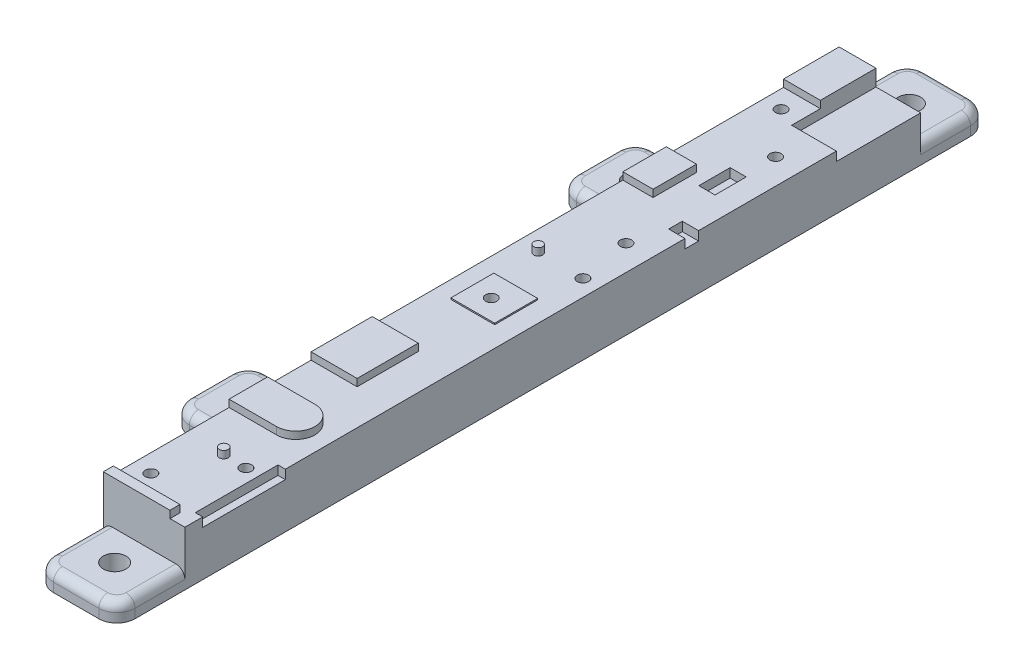
SolidWorks part; units mm, degrees
ref_plane "Front Plane" through (0, 0, 0) normal (0, 0, 1) x (1, 0, 0)
ref_plane "Top Plane" through (0, 0, 0) normal (0, 1, 0) x (1, 0, 0)
ref_plane "Right Plane" through (0, 0, 0) normal (1, 0, 0) x (0, 0, -1)
sketch "Sketch1" plane through (0, 0, 0) normal (0, 1, 0) x (1, 0, 0)
  line L1 (0, 0) -> (-18, 0)
  line L2 (0, 0) -> (0, -162.4)
  line L3 (0, -162.4) -> (-18, -162.4)
  line L4 (-18, 0) -> (-18, -162.4)
  line L5 (-18, 0) -> (-9.87, 0)
  line L6 (-18, 0) -> (-18, -12.28)
  line L7 (-18, -12.28) -> (-9.87, -12.28)
  line L8 (-9.87, 0) -> (-9.87, -12.28)
  line L9 (-18, -38.15) -> (-11.34, -38.15)
  line L10 (-18, -38.15) -> (-18, -47.73)
  line L11 (-18, -47.73) -> (-11.34, -47.73)
  line L12 (-11.34, -38.15) -> (-11.34, -47.73)
  line L13 (-18, -103.06) -> (-7.83, -103.06)
  line L14 (-18, -103.06) -> (-18, -116.55)
  line L15 (-18, -116.55) -> (-7.83, -116.55)
  line L16 (-7.83, -103.06) -> (-7.83, -116.55)
  line L17 (-18, -160.19) -> (-3.29, -160.19)
  line L18 (-18, -160.19) -> (-18, -162.4)
  line L19 (-18, -162.4) -> (-3.29, -162.4)
  line L20 (-3.29, -160.19) -> (-3.29, -162.4)
  line L21 (-14.18, -80.03) -> (-4.51, -80.03)
  line L22 (-14.18, -80.03) -> (-14.18, -89.52)
  line L23 (-14.18, -89.52) -> (-4.51, -89.52)
  line L24 (-4.51, -80.03) -> (-4.51, -89.52)
  line L25 (-18, -126.15) -> (-7.53, -126.15)
  line L26 (-18, -126.15) -> (-18, -134.64)
  line L27 (-18, -134.64) -> (-7.53, -134.64)
  line L28 (-7.53, -126.15) -> (-7.53, -134.64)
  arc A0 (-7.53, -134.64) -> (-7.53, -126.15) centre (-7.53, -130.395) ccw
  dimension "D1" = 162.4
  dimension "D2" = 18
  dimension "D3" = 14.71
  dimension "D4" = 2.21
  dimension "D5" = 8.49
  dimension "D6" = 27.76
  dimension "D7" = 10.47
  dimension "D8" = 13.49
  dimension "D9" = 45.85
  dimension "D10" = 10.17
  dimension "D11" = 8.13
  dimension "D12" = 12.28
  dimension "D13" = 9.58
  dimension "D14" = 6.66
  dimension "D15" = 38.15
  dimension "D16" = 9.49
  dimension "D17" = 9.67
  dimension "D18" = 3.82
  dimension "D19" = 72.88
extrude "Boss-Extrude1" add sketch "Sketch1" against normal blind 12 contours A0 L27 L4 L17 L20 L3 L2 L1 L8 L7 L9 L12 L11 L13 L16 L15 L25 L21 L24 L23 L22 | L24 L21 L22 L23 | L12 L9 L4 L11 | L8 L1 L4 L7 | L16 L13 L4 L15 | L28 L25 L4 L27 | L28 A0 | L20 L17 L4 L3 region at (-1.6339, 0, 81.2) region at (-13.935, 0, 6.14) region at (-10.645, 0, 161.295) region at (-14.67, 0, 42.94) region at (-12.765, 0, 130.395) region at (-12.915, 0, 109.805) region at (-5.7284, 0, 130.395) region at (-9.345, 0, 84.775)
extrude "Boss-Extrude2" add sketch "Sketch1<4>" along normal blind 1.6 contours L20 L17 L4 L3 | L28 L25 L4 L27 | L28 A0 | L16 L13 L4 L15 | L12 L9 L4 L11 | L8 L1 L4 L7 region at (-13.935, 0, 6.14) region at (-10.645, 0, 161.295) region at (-14.67, 0, 42.94) region at (-12.765, 0, 130.395) region at (-12.915, 0, 109.805) region at (-5.7284, 0, 130.395)
sketch "Sketch1<4>" plane through (0, 0, 0) normal (0, 1, 0) x (1, 0, 0) same geometry as "Sketch1"
extrude "Boss-Extrude3" add sketch "Sketch1<5>" along normal blind 0.3 contours L24 L21 L22 L23 region at (-9.345, 0, 84.775)
sketch "Sketch1<5>" plane through (0, 0, 0) normal (0, 1, 0) x (1, 0, 0) same geometry as "Sketch1"
sketch "Sketch2" plane through (0, 0, 162.4) normal (0, 0, 1) x (1, 0, 0)
  line L0 (-18, -12) -> (-18, 1.6) construction
  line L1 (-18, -8) -> (0, -8)
  line L2 (-18, -8) -> (-18, -12)
  line L3 (-18, -12) -> (0, -12)
  line L4 (0, -8) -> (0, -12)
  dimension "D1" = 4
extrude "Boss-Extrude4" add sketch "Sketch2" along normal blind 15
sketch "Sketch3" plane through (0, 0, 0) normal (0, 0, -1) x (-1, 0, 0)
  line L0 (0, -12) -> (0, 0) construction
  line L1 (0, -8) -> (18, -8)
  line L2 (0, -8) -> (0, -12)
  line L3 (0, -12) -> (18, -12)
  line L4 (18, -8) -> (18, -12)
  dimension "D1" = 4
extrude "Boss-Extrude5" add sketch "Sketch3" along normal blind 15
sketch "Sketch4" plane through (-18, 0, 0) normal (-1, 0, 0) x (0, 0, 1)
  line L0 (-15, -12) -> (177.4, -12) construction
  line L1 (30, -12) -> (47, -12)
  line L2 (30, -12) -> (30, -8)
  line L3 (30, -8) -> (47, -8)
  line L4 (47, -12) -> (47, -8)
  line L5 (-15, -12) -> (-15, -8) construction
  line L6 (115.4, -12) -> (132.4, -12)
  line L7 (115.4, -12) -> (115.4, -8)
  line L8 (115.4, -8) -> (132.4, -8)
  line L9 (132.4, -12) -> (132.4, -8)
  line L10 (177.4, -8) -> (177.4, -12) construction
  dimension "D1" = 17
  dimension "D2" = 45
  dimension "D3" = 45
  dimension "D4" = 4
extrude "Boss-Extrude6" add sketch "Sketch4" along normal blind 15
fillet "Fillet1" radius 4 8 edges at (0, -10, 177.4) (-18, -10, 177.4) (-33, -10, 132.4) (-33, -10, 115.4) (-33, -10, 47) (-33, -10, 30) (0, -10, -15) (-18, -10, -15)
fillet "Fillet2" radius 2 20 edges at (-23.5, -8, 115.4) (-31.8284, -8, 116.5716) (-33, -8, 123.9) (-31.8284, -8, 131.2284) (0, -8, 167.9) (-1.1716, -8, 176.2284) (-9, -8, 177.4) (-16.8284, -8, 176.2284) (-23.5, -8, 47) (-31.8284, -8, 45.8284) (-33, -8, 38.5) (-31.8284, -8, 31.1716) (0, -8, -5.5) (-1.1716, -8, -13.8284) (-9, -8, -15) (-16.8284, -8, -13.8284) (-23.5, -8, 132.4) (-18, -8, 167.9) (-23.5, -8, 30) (-18, -8, -5.5)
sketch "Sketch5" plane through (0, -8, 0) normal (0, 1, 0) x (1, 0, 0)
  line L0 (-18, -45) -> (-18, -32) construction
  line L1 (-18, -32) -> (-29, -32) construction
  line L2 (-18, -117.4) -> (-29, -117.4) construction
  line L3 (-2, -162.4) -> (-16, -162.4) construction
  line L4 (-16, 0) -> (-2, 0) construction
  line L5 (-2, 0) -> (-2, 11) construction
  circle A0 centre (-9, 6.5) radius 2.5
  circle A1 centre (-24.5, -38.5) radius 2.5
  circle A2 centre (-24.5, -123.9) radius 2.5
  circle A3 centre (-9, -168.9) radius 2.5
  point P8 (0, 0)
  point P9 (0, 0)
  dimension "D1" = 5
  dimension "D2" = 6.5
  dimension "D3" = 6.5
  dimension "D4" = 6.5
  dimension "D5" = 6.5
  dimension "D6" = 6.5
  dimension "D7" = 7
extrude "Cut-Extrude1" cut sketch "Sketch5" against normal up to next
sketch "Sketch6" plane through (0, 0, 0) normal (0, 1, 0) x (1, 0, 0)
  line L0 (-18, -134.64) -> (-18, -160.19) construction
  line L1 (-18, -160.19) -> (-3.29, -160.19) construction
  circle A0 centre (-14.04, -155.86) radius 1.25
  circle A1 centre (-9.46, -144.3448) radius 0.985
  circle A2 centre (-4.59, -144.3448) radius 1.25
  point P10 (0, 0)
  dimension "D1" = 2.5
  dimension "D4" = 2.5
  dimension "D5" = 1.97
  dimension "D2" = 3.96
  dimension "D3" = 4.33
  dimension "D6" = 8.54
  dimension "D7" = 13.41
extrude "Boss-Extrude7" add sketch "Sketch6" along normal blind 1.6 contours A1 region at (-9.46, 0, 144.3448)
extrude "Cut-Extrude2" cut sketch "Sketch6<3>" against normal up to next contours A0 | A2 region at (-14.04, 0, 155.86) region at (-4.59, 0, 144.3448)
sketch "Sketch6<3>" plane through (0, 0, 0) normal (0, 1, 0) x (1, 0, 0) same geometry as "Sketch6"
sketch "Sketch7" plane through (0, 0.3, 0) normal (0, 1, 0) x (1, 0, 0)
  line L0 (-18, -47.73) -> (-18, -103.06) construction
  line L1 (-18, -160.19) -> (-3.29, -160.19) construction
  circle A0 centre (-9.705, -85.075) radius 1.25
  point P2 (0, 0)
  dimension "D1" = 2.5
  dimension "D2" = 8.295
  dimension "D3" = 75.115
extrude "Cut-Extrude3" cut sketch "Sketch7" against normal up to next
sketch "Sketch8" plane through (0, 0, 0) normal (0, 1, 0) x (1, 0, 0)
  line L0 (-18, -47.73) -> (-18, -103.06) construction
  line L1 (0, -162.4) -> (-3.29, -162.4) construction
  circle A0 centre (-13.505, -70.905) radius 0.97
  circle A1 centre (-3.64, -70.905) radius 1.25
  point P4 (0, 0)
  dimension "D1" = 1.94
  dimension "D2" = 2.5
  dimension "D5" = 91.495
  dimension "D3" = 4.495
  dimension "D4" = 14.36
extrude "Boss-Extrude8" add sketch "Sketch8" along normal blind 1.6 contours A0 region at (-13.505, 0, 70.905)
extrude "Cut-Extrude4" cut sketch "Sketch8<3>" against normal up to next contours A1 region at (-3.64, 0, 70.905)
sketch "Sketch8<3>" plane through (0, 0, 0) normal (0, 1, 0) x (1, 0, 0) same geometry as "Sketch8"
sketch "Sketch9" plane through (0, 0, 0) normal (0, 1, 0) x (1, 0, 0)
  line L0 (-18, -47.73) -> (-18, -103.06) construction
  line L1 (0, 0) -> (-9.87, 0) construction
  line L2 (-18, -12.28) -> (-18, -38.15) construction
  line L3 (-18, -12.28) -> (-9.87, -12.28) construction
  line L4 (-9.87, 0) -> (-9.87, -12.28) construction
  line L5 (0, 0) -> (-9.87, 0)
  line L6 (0, 0) -> (0, -18.61)
  line L7 (0, -18.61) -> (-9.87, -18.61)
  line L8 (-9.87, 0) -> (-9.87, -18.61)
  circle A0 centre (-5.61, -59.44) radius 1.25
  circle A1 centre (-5.61, -26.42) radius 1.25
  circle A2 centre (-14.09, -16.73) radius 1.25
  point P22 (0, 0)
  line M12 (-9.87, 0) -> (-9.87, -12.28)
  line M30 (0, -162.4) -> (0, 0)
  line M31 (0, 0) -> (-9.87, 0)
  dimension "D1" = 2.5
  dimension "D4" = 2.5
  dimension "D6" = 2.5
  dimension "D2" = 12.39
  dimension "D3" = 59.44
  dimension "D5" = 26.42
  dimension "D7" = 3.91
  dimension "D8" = 4.45
  dimension "D9" = 18.61
extrude "Cut-Extrude5" cut sketch "Sketch9" against normal up to next contours A0 | A1 | A2 region at (-5.61, 0, 59.44) region at (-5.61, 0, 26.42) region at (-14.09, 0, 16.73)
extrude "Cut-Extrude6" cut sketch "Sketch9<3>" against normal blind 1.6
sketch "Sketch9<3>" plane through (0, 0, 0) normal (0, 1, 0) x (1, 0, 0) same geometry as "Sketch9"
extrude "Cut-Extrude9" cut sketch "Sketch9<4>" against normal blind 2 contours L8 L7 M12 M30 M31 region at (-4.935, 0, 9.305)
sketch "Sketch9<4>" plane through (0, 0, 0) normal (0, 1, 0) x (1, 0, 0) same geometry as "Sketch9"
sketch "Sketch11" plane through (0, 0, 0) normal (0, 1, 0) x (1, 0, 0)
  line L0 (0, 0) -> (-9.87, 0) construction
  line L1 (-8.56, -33.5) -> (-5, -33.5)
  line L2 (-8.56, -33.5) -> (-8.56, -40.4)
  line L3 (-8.56, -40.4) -> (-5, -40.4)
  line L4 (-5, -33.5) -> (-5, -40.4)
  line L5 (-18, -12.28) -> (-18, -38.15) construction
  dimension "D1" = 33.5
  dimension "D2" = 40.4
  dimension "D3" = 13
  dimension "D4" = 9.44
extrude "Cut-Extrude10" cut sketch "Sketch11" against normal blind 2
sketch "Sketch14" plane through (0, 0, 0) normal (0, 1, 0) x (1, 0, 0)
  line L0 (0, -18.61) -> (0, -162.4) construction
  line L1 (0, -49.02) -> (-3.6, -49.02)
  line L2 (0, -49.02) -> (0, -52.02)
  line L3 (0, -52.02) -> (-3.6, -52.02)
  line L4 (-3.6, -49.02) -> (-3.6, -52.02)
  line L5 (0, 0) -> (-9.87, 0) construction
  line L6 (-18, -47.73) -> (-18, -103.06) construction
  dimension "D1" = 49.02
  dimension "D2" = 52.02
  dimension "D3" = 14.4
extrude "Cut-Extrude11" cut sketch "Sketch14" against normal blind 2
sketch "Sketch15" plane through (0, 0, 0) normal (0, 1, 0) x (1, 0, 0)
  line L0 (0, -52.02) -> (0, -162.4) construction
  line L1 (0, -158.46) -> (-1.63, -158.46)
  line L2 (0, -158.46) -> (0, -140.22)
  line L3 (0, -140.22) -> (-1.63, -140.22)
  line L4 (-1.63, -158.46) -> (-1.63, -140.22)
  line L5 (-18, -134.64) -> (-18, -160.19) construction
  line L6 (0, -162.4) -> (-3.29, -162.4) construction
  dimension "D1" = 16.37
  dimension "D2" = 3.94
  dimension "D3" = 22.18
extrude "Cut-Extrude12" cut sketch "Sketch15" against normal blind 2
